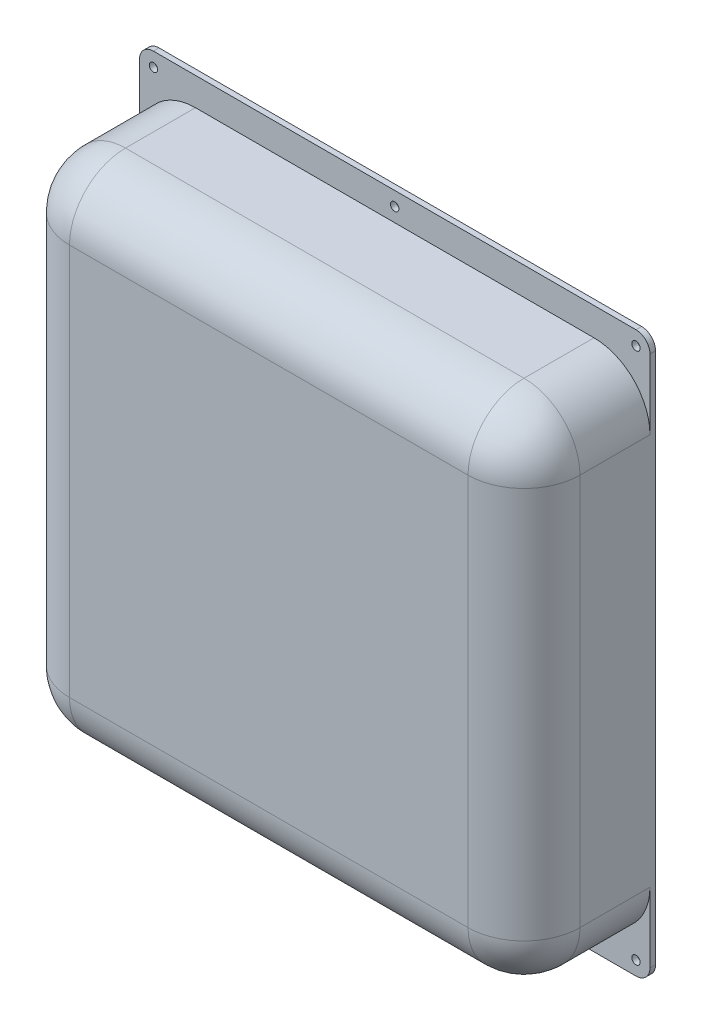
SolidWorks part; units mm, degrees
ref_plane "Front Plane" through (0, 0, 0) normal (0, 0, 1) x (1, 0, 0)
ref_plane "Top Plane" through (0, 0, 0) normal (0, 1, 0) x (1, 0, 0)
ref_plane "Right Plane" through (0, 0, 0) normal (1, 0, 0) x (0, 0, -1)
sketch "Sketch1" plane through (0, 0, 0) normal (0, 0, 1) x (1, 0, 0)
  line L1 (86.195, 100) -> (-86.195, 100)
  line L2 (91.195, 95) -> (91.195, -95)
  line L3 (86.195, -100) -> (-86.195, -100)
  line L4 (-91.195, 95) -> (-91.195, -95)
  circle A0 centre (86.195, -95) radius 1.5 construction
  circle A1 centre (0, -95) radius 1.5 construction
  circle A2 centre (-86.195, -95) radius 1.5 construction
  circle A3 centre (-86.195, 95) radius 1.5 construction
  circle A4 centre (0, 95) radius 1.5 construction
  circle A5 centre (86.195, 95) radius 1.5 construction
  circle A6 centre (86.195, -95) radius 1.5
  circle A7 centre (0, -95) radius 1.5
  circle A8 centre (-86.195, -95) radius 1.5
  circle A9 centre (-86.195, 95) radius 1.5
  circle A10 centre (0, 95) radius 1.5
  circle A11 centre (86.195, 95) radius 1.5
  arc A12 (91.195, -95) -> (86.195, -100) centre (86.195, -95) cw
  arc A13 (86.195, 100) -> (91.195, 95) centre (86.195, 95) cw
  arc A14 (-86.195, 100) -> (-91.195, 95) centre (-86.195, 95) ccw
  arc A15 (-86.195, -100) -> (-91.195, -95) centre (-86.195, -95) cw
  dimension "D5" = 5
  dimension "D1" = 5
  dimension "D2" = 5
  dimension "D3" = 5
  dimension "D4" = 5
extrude "Boss-Extrude1" add sketch "Sketch1" along normal blind 2
sketch "Sketch2" plane through (0, 0, 2) normal (0, 0, 1) x (1, 0, 0)
  line L0 (91.195, -95) -> (91.195, 95) construction
  line L1 (91.195, -90) -> (-91.195, -90)
  line L2 (91.195, -90) -> (91.195, 90)
  line L3 (91.195, 90) -> (-91.195, 90)
  line L4 (-91.195, -90) -> (-91.195, 90)
  line L5 (-91.195, 95) -> (-91.195, -95) construction
  line L6 (-86.195, -100) -> (86.195, -100) construction
  line L7 (86.195, 100) -> (-86.195, 100) construction
  dimension "D1" = 10
  dimension "D2" = 10
extrude "Boss-Extrude2" add sketch "Sketch2" along normal blind 45
fillet "Fillet1" radius 20 8 edges at (-91.195, -90, 24.5) (91.195, -90, 24.5) (-91.195, 90, 24.5) (-91.195, 0, 47) (91.195, 0, 47) (91.195, 90, 24.5) (0, 90, 47) (0, -90, 47)
shell "Shell1" thickness 2 removed face at (1.5, 95, 0)
